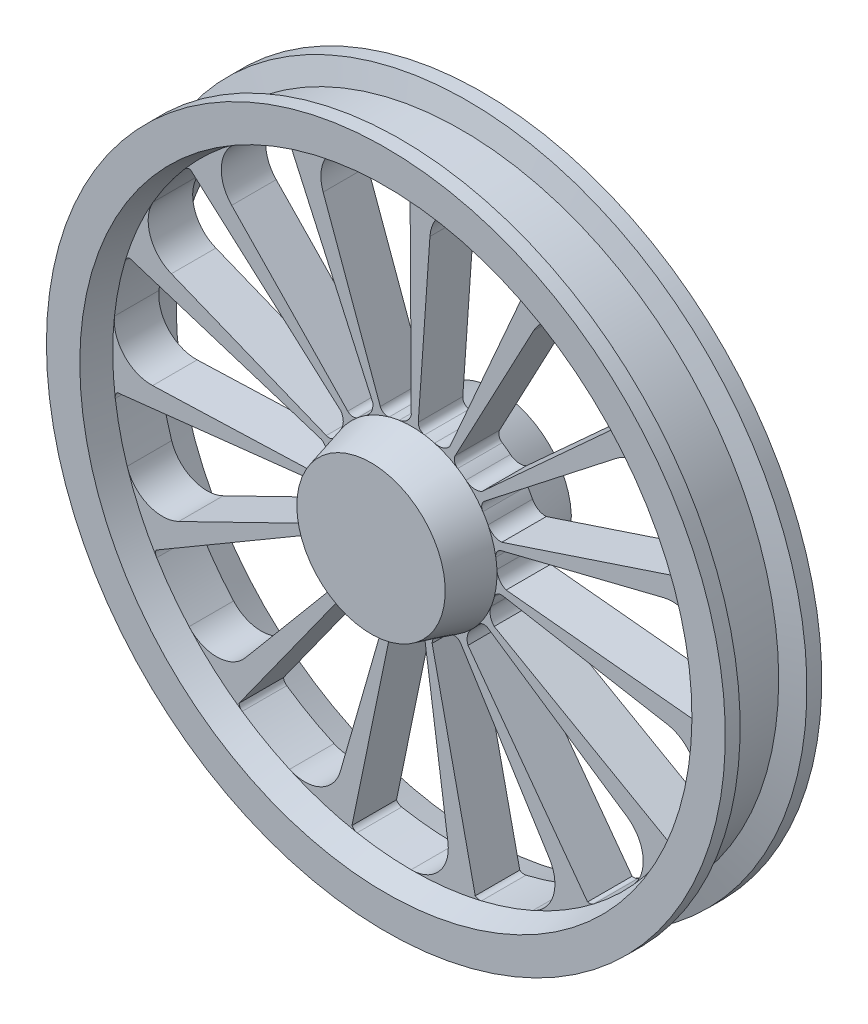
SolidWorks part; units mm, degrees
material "1060 Alloy"
ref_plane "Front Plane" through (0, 0, 0) normal (0, 0, 1) x (1, 0, 0)
ref_plane "Top Plane" through (0, 0, 0) normal (0, 1, 0) x (1, 0, 0)
ref_plane "Right Plane" through (0, 0, 0) normal (1, 0, 0) x (0, 0, -1)
sketch "Sketch3" plane through (0, 0, 0) normal (1, 0, 0) x (0, 0, -1)
  line L1 (-85, -159.784) -> (-85, -259.784)
  line L2 (-36.9615, 167.716) -> (36.9615, 167.716)
  line L3 (36.9615, 167.716) -> (45, 197.716)
  line L4 (45, 197.716) -> (65, 197.716)
  line L5 (65, 197.716) -> (65, 152.716)
  line L6 (65, 152.716) -> (30, 143.3378)
  line L7 (30, 143.3378) -> (30, -145.0468)
  line L8 (30, -145.0468) -> (85, -159.784)
  line L9 (85, -159.784) -> (85, -259.784)
  line L10 (85, -259.784) -> (-85, -259.784)
  line L11 (-30, -145.0468) -> (-85, -159.784)
  line L12 (-30, 143.3378) -> (-30, -145.0468)
  line L13 (-65, 152.716) -> (-30, 143.3378)
  line L14 (-65, 197.716) -> (-65, 152.716)
  line L15 (-45, 197.716) -> (-65, 197.716)
  line L16 (-36.9615, 167.716) -> (-45, 197.716)
  point P4 (0, 0)
  point P8 (0, 0)
  point P36 (0, 167.716)
  dimension "D1" = 130
  dimension "D2" = 45
  dimension "D3" = 30
revolve "Revolve1" add sketch "Sketch3" angle 360 about L10
sketch "Sketch4" plane through (0, 0, -30) normal (0, 0, -1) x (-1, 0, 0)
  line L0 (0, 133.2106) -> (0, -126.5394)
  line L1 (42.5253, -142.9466) -> (119.5579, 68.6987)
  line L2 (52.6577, -143.4341) -> (166.2146, 107.476)
  line L3 (159.8453, 99.2344) -> (54.1954, -138.059)
  line L4 (86.3708, -170.3444) -> (242.8276, -8.3287)
  line L5 (95.429, -174.9108) -> (301.2227, 8.1191)
  line L6 (292.0519, 3.1807) -> (99.02, -170.626)
  line L7 (115.2821, -213.207) -> (324.1101, -128.835)
  line L8 (121.6997, -221.063) -> (384.1466, -137.5606)
  line L9 (373.76, -138.342) -> (126.7231, -218.6092)
  line L10 (124.26, -264.1232) -> (349.3511, -271.9836)
  line L11 (126.9275, -273.9103) -> (400.6481, -304.3739)
  line L12 (390.8417, -300.8631) -> (132.5146, -273.7118)
  line L13 (111.7522, -314.2892) -> (314.186, -413.0228)
  line L14 (110.2083, -324.3151) -> (347.8739, -463.4771)
  line L15 (340.3433, -456.2813) -> (115.3932, -326.4063)
  line L16 (79.9215, -355.0307) -> (224.6954, -527.5656)
  line L17 (74.4332, -363.5618) -> (234.9492, -587.36)
  line L18 (230.9964, -577.7233) -> (78.3192, -367.5811)
  line L19 (34.2716, -379.3032) -> (96.3529, -595.8065)
  line L20 (25.7878, -384.8645) -> (81.3996, -654.602)
  line L21 (81.7082, -644.1907) -> (27.7031, -390.1168)
  line L22 (-17.3042, -382.9097) -> (-48.6499, -605.9461)
  line L23 (-27.3165, -384.5395) -> (-86.2247, -653.5764)
  line L24 (-81.7082, -644.1907) -> (-27.7031, -390.1168)
  line L25 (-65.8879, -365.2267) -> (-185.2407, -556.2311)
  line L26 (-75.6975, -362.6433) -> (-238.94, -584.4605)
  line L27 (-230.9964, -577.7233) -> (-78.3192, -367.5811)
  line L28 (-103.079, -329.3116) -> (-289.8017, -455.2577)
  line L29 (-110.9897, -322.9617) -> (-350.3404, -459.2051)
  line L30 (-340.3433, -456.2813) -> (-115.3932, -326.4063)
  line L31 (-122.4468, -281.3747) -> (-344.2533, -320.4851)
  line L32 (-127.0908, -272.3561) -> (-401.1637, -299.4679)
  line L33 (-390.8417, -300.8631) -> (-132.5146, -273.7118)
  line L34 (-120.6424, -229.7045) -> (-339.1805, -175.2168)
  line L35 (-121.2168, -219.5767) -> (-382.6222, -132.8691)
  line L36 (-373.76, -138.342) -> (-126.7231, -218.6092)
  line L37 (-97.9779, -183.2353) -> (-275.4602, -44.5709)
  line L38 (-94.3832, -173.7495) -> (-297.9219, 11.785)
  line L39 (-292.0519, 3.1807) -> (-99.02, -170.626)
  line L40 (-58.3721, -150.0021) -> (-164.1104, 48.8627)
  line L41 (-51.23, -142.7984) -> (-161.7081, 109.4824)
  line L42 (-159.8453, 99.2344) -> (-54.1954, -138.059)
  line L43 (-8.6732, -135.7512) -> (-24.3844, 88.9285)
  line L44 (0.7814, -132.0752) -> (2.4665, 143.3302)
  arc A0 (236.1508, 66.9268) -> (173.2792, 104.1961) centre (0, -259.784) ccw
  circle A1 centre (0, -259.784) radius 114.7372 construction
  circle A2 centre (0, -259.784) radius 403.1218 construction
  arc A3 (30.4725, -149.1673) -> (17.0313, -146.3179) centre (0, -259.784) ccw
  arc A4 (82.8493, 134.7324) -> (10.2544, 143.2073) centre (0, -259.784) ccw
  arc A5 (17.0313, -146.3179) -> (0, -126.5394) centre (20, -126.5394) cw
  arc A6 (30.4725, -149.1673) -> (42.5253, -142.9466) centre (33.1284, -139.5264) ccw
  arc A7 (10.2544, 143.2073) -> (0, 133.2106) centre (10, 133.2106) ccw
  arc A8 (82.8493, 134.7324) -> (119.5579, 68.6987) centre (72.5733, 85.7997) cw
  arc A9 (173.2792, 104.1961) -> (159.8453, 99.2344) centre (168.9807, 95.167) ccw
  arc A10 (236.1508, 66.9268) -> (242.8276, -8.3287) centre (206.8606, 26.4042) cw
  arc A11 (72.8299, -171.1249) -> (86.3708, -170.3444) centre (79.1774, -163.3978) ccw
  arc A12 (61.7097, -163.0548) -> (54.1954, -138.059) centre (72.4664, -146.1938) cw
  arc A13 (72.8299, -171.1249) -> (61.7097, -163.0548) centre (0, -259.784) ccw
  arc A14 (348.6198, -57.37) -> (306.3424, 2.2494) centre (0, -259.784) ccw
  arc A15 (306.3424, 2.2494) -> (292.0519, 3.1807) centre (298.7432, -4.2507) ccw
  arc A16 (348.6198, -57.37) -> (324.1101, -128.835) centre (305.3798, -82.4758) cw
  arc A17 (102.5943, -208.4125) -> (115.2821, -213.207) centre (111.536, -203.9352) ccw
  arc A18 (95.7179, -196.517) -> (99.02, -170.626) centre (112.4026, -185.4889) cw
  arc A19 (102.5943, -208.4125) -> (95.7179, -196.517) centre (0, -259.784) ccw
  arc A20 (400.8092, -216.6661) -> (386.4363, -145.0053) centre (0, -259.784) ccw
  arc A21 (386.4363, -145.0053) -> (373.76, -138.342) centre (376.8502, -147.8526) ccw
  arc A22 (400.8092, -216.6661) -> (349.3511, -271.9836) centre (351.096, -222.0141) cw
  arc A23 (114.6193, -254.5827) -> (124.26, -264.1232) centre (124.609, -254.1293) ccw
  arc A24 (113.1757, -240.9187) -> (126.7231, -218.6092) centre (132.9035, -237.6303) cw
  arc A25 (114.6193, -254.5827) -> (113.1757, -240.9187) centre (0, -259.784) ccw
  arc A26 (383.6951, -383.4176) -> (399.7118, -312.1063) centre (0, -259.784) ccw
  arc A27 (399.7118, -312.1063) -> (390.8417, -300.8631) centre (389.7964, -310.8083) ccw
  arc A28 (383.6951, -383.4176) -> (314.186, -413.0228) centre (336.1046, -368.0831) cw
  arc A29 (106.8255, -301.6522) -> (111.7522, -314.2892) centre (116.1359, -305.3012) ccw
  arc A30 (111.0643, -288.5824) -> (132.5146, -273.7118) centre (130.4241, -293.6023) cw
  arc A31 (106.8255, -301.6522) -> (111.0643, -288.5824) centre (0, -259.784) ccw
  arc A32 (300.2366, -528.7917) -> (343.8735, -470.1602) centre (0, -259.784) ccw
  arc A33 (343.8735, -470.1602) -> (340.3433, -456.2813) centre (335.3433, -464.9415) ccw
  arc A34 (300.2366, -528.7917) -> (224.6954, -527.5656) centre (262.9976, -495.4262) cw
  arc A35 (80.5606, -341.4823) -> (79.9215, -355.0307) centre (87.5819, -348.6028) ccw
  arc A36 (89.7489, -331.2666) -> (115.3932, -326.4063) centre (105.3932, -343.7268) cw
  arc A37 (80.5606, -341.4823) -> (89.7489, -331.2666) centre (0, -259.784) ccw
  arc A38 (164.8644, -627.652) -> (228.5764, -591.8382) centre (0, -259.784) ccw
  arc A39 (228.5764, -591.8382) -> (230.9964, -577.7233) centre (222.9062, -583.6011) ccw
  arc A40 (164.8644, -627.652) -> (96.3529, -595.8065) centre (144.416, -582.0246) cw
  arc A41 (40.3661, -367.1861) -> (34.2716, -379.3032) centre (43.8842, -376.5468) ccw
  arc A42 (52.9151, -361.5907) -> (78.3192, -367.5811) centre (62.1389, -379.3368) cw
  arc A43 (40.3661, -367.1861) -> (52.9151, -361.5907) centre (0, -259.784) ccw
  arc A44 (0.9858, -662.9046) -> (73.7563, -656.101) centre (0, -259.784) ccw
  arc A45 (73.7563, -656.101) -> (81.7082, -644.1907) centre (71.9267, -646.2698) ccw
  arc A46 (0.9858, -662.9046) -> (-48.6499, -605.9461) centre (0.8635, -612.9047) cw
  arc A47 (-6.8081, -374.319) -> (-17.3042, -382.9097) centre (-7.4015, -384.3014) ccw
  arc A48 (6.9319, -374.3116) -> (27.7031, -390.1168) centre (8.1402, -394.2751) cw
  arc A49 (-6.8081, -374.319) -> (6.9319, -374.3116) centre (0, -259.784) ccw
  arc A50 (-163.0634, -628.4539) -> (-93.8169, -651.837) centre (0, -259.784) ccw
  arc A51 (-93.8169, -651.837) -> (-81.7082, -644.1907) centre (-91.4896, -642.1116) ccw
  arc A52 (-163.0634, -628.4539) -> (-185.2407, -556.2311) centre (-142.8383, -582.727) cw
  arc A53 (-52.8051, -361.6478) -> (-65.8879, -365.2267) centre (-57.4074, -370.5259) ccw
  arc A54 (-40.25, -367.2296) -> (-27.7031, -390.1168) centre (-47.2661, -385.9586) cw
  arc A55 (-52.8051, -361.6478) -> (-40.25, -367.2296) centre (0, -259.784) ccw
  arc A56 (-298.9174, -530.2569) -> (-245.1683, -579.7835) centre (0, -259.784) ccw
  arc A57 (-245.1683, -579.7835) -> (-230.9964, -577.7233) centre (-239.0866, -571.8454) ccw
  arc A58 (-298.9174, -530.2569) -> (-289.8017, -455.2577) centre (-261.842, -496.7096) cw
  arc A59 (-89.6717, -331.3635) -> (-103.079, -329.3116) centre (-97.4871, -337.602) ccw
  arc A60 (-80.4723, -341.5693) -> (-78.3192, -367.5811) centre (-94.4995, -355.8254) cw
  arc A61 (-89.6717, -331.3635) -> (-80.4723, -341.5693) centre (0, -259.784) ccw
  arc A62 (-383.0858, -385.2926) -> (-354.1279, -452.3991) centre (0, -259.784) ccw
  arc A63 (-354.1279, -452.3991) -> (-340.3433, -456.2813) centre (-345.3433, -447.621) ccw
  arc A64 (-383.0858, -385.2926) -> (-344.2533, -320.4851) centre (-335.5709, -369.7255) cw
  arc A65 (-111.0331, -288.7023) -> (-122.4468, -281.3747) centre (-120.7103, -291.2227) ccw
  arc A66 (-106.7802, -301.7676) -> (-115.3932, -326.4063) centre (-125.3932, -309.0858) cw
  arc A67 (-111.0331, -288.7023) -> (-106.7802, -301.7676) centre (0, -259.784) ccw
  arc A68 (-401.0153, -218.6268) -> (-401.8556, -291.7099) centre (0, -259.784) ccw
  arc A69 (-401.8556, -291.7099) -> (-390.8417, -300.8631) centre (-391.887, -290.9179) ccw
  arc A70 (-401.0153, -218.6268) -> (-339.1805, -175.2168) centre (-351.2766, -223.7316) cw
  arc A71 (-113.196, -241.041) -> (-120.6424, -229.7045) centre (-123.0616, -239.4074) ccw
  arc A72 (-114.6248, -254.7065) -> (-132.5146, -273.7118) centre (-134.6052, -253.8214) cw
  arc A73 (-113.196, -241.041) -> (-114.6248, -254.7065) centre (0, -259.784) ccw
  arc A74 (-349.6055, -59.0774) -> (-380.0988, -125.5003) centre (0, -259.784) ccw
  arc A75 (-380.0988, -125.5003) -> (-373.76, -138.342) centre (-370.6699, -128.8314) ccw
  arc A76 (-349.6055, -59.0774) -> (-275.4602, -44.5709) centre (-306.2433, -83.9714) cw
  arc A77 (-95.7862, -196.6205) -> (-97.9779, -183.2353) centre (-104.1345, -191.1154) ccw
  arc A78 (-102.6498, -208.5233) -> (-126.7231, -218.6092) centre (-120.5428, -199.588) cw
  arc A79 (-95.7862, -196.6205) -> (-102.6498, -208.5233) centre (0, -259.784) ccw
  arc A80 (-237.7458, 65.768) -> (-292.6194, 17.4903) centre (0, -259.784) ccw
  arc A81 (-292.6194, 17.4903) -> (-292.0519, 3.1807) centre (-285.3606, 10.6121) ccw
  arc A82 (-237.7458, 65.768) -> (-164.1104, 48.8627) centre (-208.2577, 25.3891) cw
  arc A83 (-61.8141, -163.1215) -> (-58.3721, -150.0021) centre (-67.2016, -154.6968) ccw
  arc A84 (-72.9256, -171.2036) -> (-99.02, -170.626) centre (-85.6374, -155.7631) cw
  arc A85 (-61.8141, -163.1215) -> (-72.9256, -171.2036) centre (0, -259.784) ccw
  arc A86 (-84.7777, 134.3225) -> (-154.5435, 112.5377) centre (0, -259.784) ccw
  arc A87 (-154.5435, 112.5377) -> (-159.8453, 99.2344) centre (-150.7098, 103.3018) ccw
  arc A88 (-84.7777, 134.3225) -> (-24.3844, 88.9285) centre (-74.2626, 85.4407) cw
  arc A89 (-17.1538, -146.3363) -> (-8.6732, -135.7512) centre (-18.6489, -136.4487) ccw
  arc A90 (-30.592, -149.2003) -> (-54.1954, -138.059) centre (-35.9245, -129.9243) cw
  arc A91 (-17.1538, -146.3363) -> (-30.592, -149.2003) centre (0, -259.784) ccw
  point P203 (0, -259.784)
  circle M1 centre (0, -259.784) radius 403.1218
  circle M2 centre (0, -259.784) radius 114.7372
  dimension "D2" = 20
  dimension "D3" = 10
  dimension "D4" = 10
  dimension "D5" = 50
  dimension "D1" = 20
  dimension "D6" = 4.351
  dimension "D7" = 15
extrude "Cut-Extrude1" cut sketch "Sketch4" against normal blind 100 contours A84 A83 L40 A82 A81 L38 M2 M1 | A78 A77 L37 A76 A75 L35 M2 M1 | A72 A71 L34 A70 A69 L32 M2 M1 | A66 A65 L31 A64 A63 L29 M2 M1 | A60 A59 L28 A58 A57 L26 M2 M1 | A54 A53 L25 A52 A51 L23 M2 M1 | A48 A47 L22 A46 A45 L20 M2 M1 | A42 A41 L19 A40 A39 L17 M2 M1 | A36 A35 L16 A34 A33 L14 M2 M1 | A30 A29 L13 A28 A27 L11 M2 M1 | A24 A23 L10 A22 A21 L8 M2 M1 | A18 A17 L7 A16 A15 L5 M2 M1 | A12 A11 L4 A10 A9 L2 M2 M1 | A8 A7 L44 A5 A6 L1 M1 M2 | A90 A89 L43 A88 A87 L41 M2 M1 region at (-48.4485, 18.0443, -30) region at (68.7431, 13.7306, -30) region at (-157.2629, -25.681, -30) region at (174.0483, -37.8763, -30) region at (-238.8851, -109.8848, -30) region at (249.259, -127.8531, -30) region at (-279.2019, -220.0076, -30) region at (281.3706, -240.6419, -30) region at (-271.2421, -337.0081, -30) region at (264.8306, -356.7405, -30) region at (-216.3821, -440.6558, -30) region at (202.4991, -456.0745, -30) region at (-124.1077, -513.0291, -30) region at (105.1535, -521.4681, -30) region at (-10.374, -541.6141, -30)
